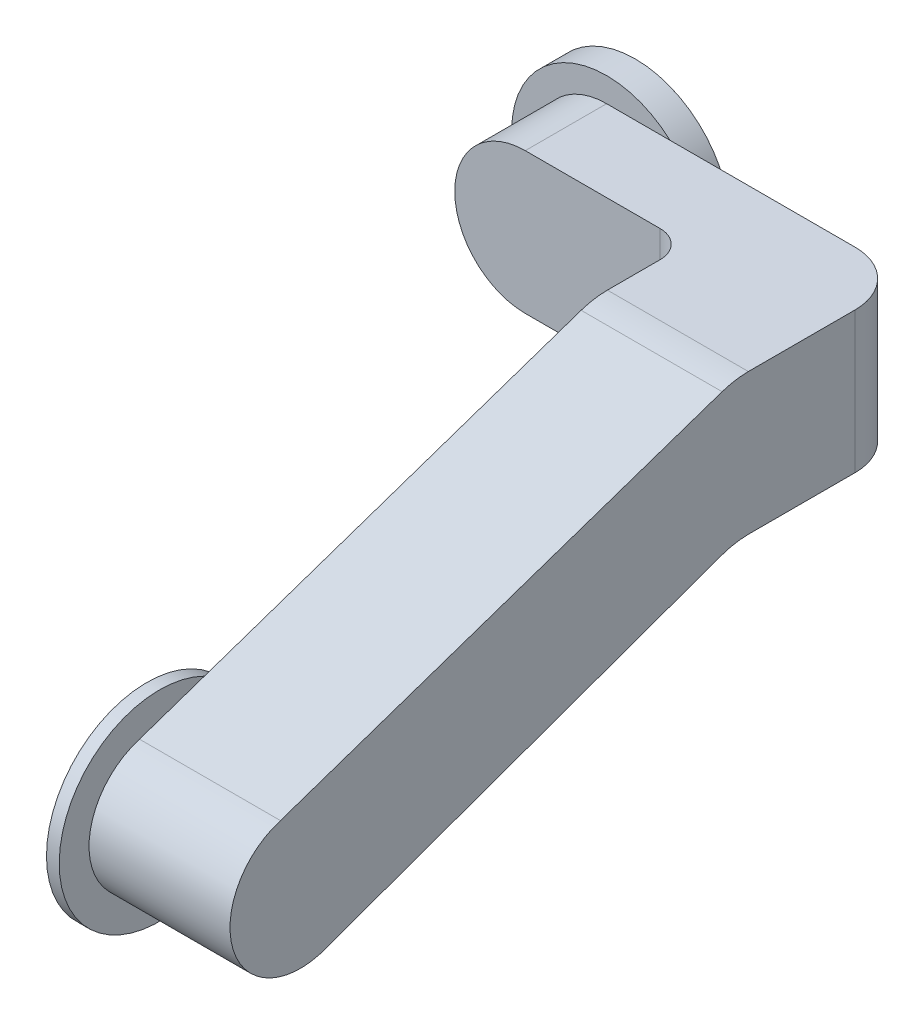
SolidWorks part; units mm, degrees
ref_plane "Front Plane" through (0, 0, 0) normal (0, 0, 1) x (1, 0, 0)
ref_plane "Top Plane" through (0, 0, 0) normal (0, 1, 0) x (1, 0, 0)
ref_plane "Right Plane" through (0, 0, 0) normal (1, 0, 0) x (0, 0, -1)
sketch "Sketch2" plane through (0, 0, 0) normal (0, 0, 1) x (1, 0, 0)
  circle A0 centre (0, 0) radius 44.45
extrude "Boss-Extrude1" add sketch "Sketch2" along normal blind 13.462
sketch "Sketch3" plane through (0, 0, 13.462) normal (0, 0, 1) x (1, 0, 0)
  line L0 (0, 33.02) -> (0, -33.02)
  arc A0 (0, 33.02) -> (0, -33.02) centre (0, 0) ccw
  dimension "D1" = 66.04
extrude "Boss-Extrude2" add sketch "Sketch3" along normal blind 38.1
sketch "Sketch4" plane through (0, 0, 0) normal (1, 0, 0) x (0, 0, -1)
  line L1 (-51.562, 33.02) -> (-13.462, 33.02)
  line L2 (-51.562, 33.02) -> (-51.562, -33.02)
  line L3 (-51.562, -33.02) -> (-13.462, -33.02)
  line L4 (-13.462, 33.02) -> (-13.462, -33.02)
extrude "Boss-Extrude3" add sketch "Sketch4" along normal blind 141.859
sketch "Sketch5" plane through (0, 18.542, 51.562) normal (0, 0, -1) x (1, 0, 0)
  line L5 (141.859, -14.478) -> (0, -14.478) construction
  line L6 (141.859, 51.562) -> (75.819, 51.562)
  line L7 (141.859, 51.562) -> (141.859, -14.478)
  line L8 (141.859, -14.478) -> (75.819, -14.478)
  line L9 (75.819, 51.562) -> (75.819, -14.478)
extrude "Boss-Extrude4" add sketch "Sketch5" against normal blind 43.6626
fillet "Fillet1" radius 25.4 1 edges at (141.859, 0, 13.462)
fillet "Fillet2" radius 12.7 1 edges at (75.819, 0, 51.562)
ref_plane "Plane1" through (0, 0, 95.2246) normal (0, 0, 1) x (0, -1, 0)
sketch "Sketch8" plane through (0, 0, 95.2246) normal (0, 0, 1) x (0, -1, 0)
  line L1 (-33.02, 75.819) -> (33.02, 75.819)
  line L2 (-33.02, 75.819) -> (-33.02, 141.859)
  line L3 (-33.02, 141.859) -> (33.02, 141.859)
  line L4 (33.02, 75.819) -> (33.02, 141.859)
ref_plane "Plane2" through (0, 0, 298.704) normal (0, 0, -1) x (-1, 0, 0)
sketch "Sketch9" plane through (0, 0, 298.704) normal (0, 0, -1) x (-1, 0, 0)
  line L0 (-141.859, 0) -> (-75.819, 0) construction
  line L1 (-141.859, 33.02) -> (-141.859, -33.02) construction
  line L2 (-75.819, 33.02) -> (-75.819, -33.02) construction
  line L3 (-108.839, 0) -> (-108.839, -71.2216) construction
  line L4 (-108.839, -71.2216) -> (-75.819, -71.2216) construction
ref_plane "Plane3" through (0, -87.2041, 293.9628) normal (0, -0.2844, 0.9587) x (-1, 0, 0)
sketch "Sketch10" plane through (0, -87.2041, 293.9628) normal (0, -0.2844, 0.9587) x (-1, 0, 0)
  line L0 (-108.839, -16.6709) -> (-108.839, 16.3491) construction
  line L1 (-108.839, 16.3491) -> (-141.859, 16.3491) construction
  line L2 (-108.839, -16.6709) -> (-75.819, -16.6709) construction
  line L3 (-141.859, 16.3491) -> (-75.819, 16.3491)
  line L4 (-141.859, 16.3491) -> (-141.859, -49.6909)
  line L5 (-141.859, -49.6909) -> (-75.819, -49.6909)
  line L6 (-75.819, 16.3491) -> (-75.819, -49.6909)
loft "Loft1" add profiles "Sketch8", "Sketch10" connector at (75.819, 33.02, 95.2246) connector at (75.819, -39.5651, 308.0949)
fillet "Fillet4" radius 38.1 2 edges
sketch "Sketch11" plane through (141.859, 0, 0) normal (1, 0, 0) x (0, 0, -1)
  line L0 (-289.3131, -102.8781) -> (-308.0949, -39.5651) construction
  line L1 (-308.0949, -39.5651) -> (-289.3131, -102.8781)
  arc A0 (-308.0949, -39.5651) -> (-289.3131, -102.8781) centre (-298.704, -71.2216) ccw
extrude "Boss-Extrude5" add sketch "Sketch11" against normal blind 66.04
sketch "Sketch12" plane through (75.819, 0, 0) normal (-1, 0, 0) x (0, 0, 1)
  circle A0 centre (298.704, -71.2216) radius 46.99
extrude "Boss-Extrude6" add sketch "Sketch12" along normal blind 5.969
ref_point "Point1"
ref_axis "Axis1" through (0, 0, 13.462) along (0, 0, -1)
ref_point "Point2"
ref_axis "Axis2" through (69.85, -71.2216, 298.704) along (1, 0, 0)
